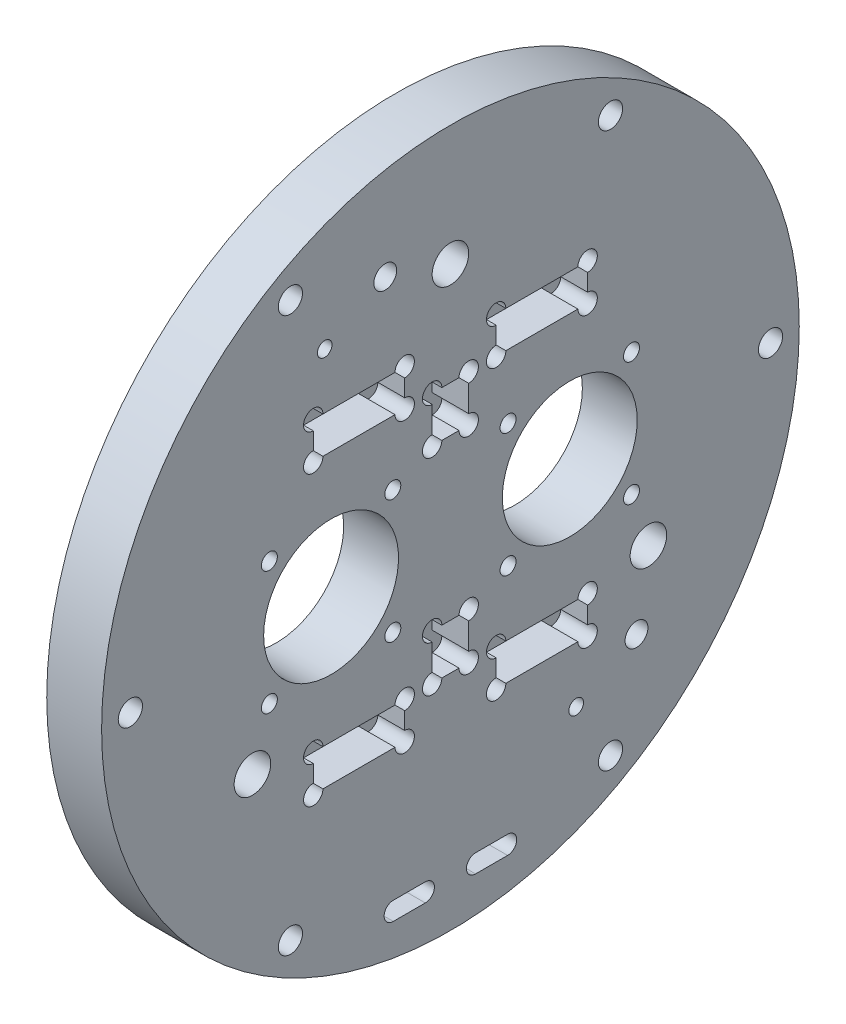
SolidWorks part; units mm, degrees
ref_plane "Front Plane" through (0, 0, 0) normal (0, 0, 1) x (1, 0, 0)
ref_plane "Top Plane" through (0, 0, 0) normal (0, 1, 0) x (1, 0, 0)
ref_plane "Right Plane" through (0, 0, 0) normal (1, 0, 0) x (0, 0, -1)
sketch "Sketch1" plane through (0, 0, 0) normal (1, 0, 0) x (0, 0, -1)
  line L0 (0, -76.29) -> (0, 76.29) construction
  line L1 (-76.29, 0) -> (76.29, 0) construction
  line L2 (26.1, 0) -> (39.5969, 13.4969) construction
  circle A0 centre (0, 0) radius 76.29
  circle A1 centre (0, 50) radius 4
  circle A2 centre (43.3013, -25) radius 4
  circle A3 centre (-43.3013, -25) radius 4
  circle A4 centre (26.1, 0) radius 14.75
  circle A5 centre (-26.1, 0) radius 14.75
  circle A6 centre (39.5969, 13.4969) radius 1.75
  circle A7 centre (39.5969, -13.4969) radius 1.75
  circle A8 centre (12.6031, -13.4969) radius 1.75
  circle A9 centre (12.6031, 13.4969) radius 1.75
  circle A10 centre (-39.5969, -13.4969) radius 1.75
  circle A11 centre (-12.6031, -13.4969) radius 1.75
  circle A12 centre (-12.6031, 13.4969) radius 1.75
  circle A13 centre (-39.5969, 13.4969) radius 1.75
  circle A14 centre (26.1, 0) radius 22.1 construction
  circle A15 centre (-26.1, 0) radius 22.1 construction
  circle A16 centre (-22.3739, -41.5) radius 2.5 construction
  point P12 (0, 0)
  point P29 (26.1, 0)
  point P37 (-4, 0)
  point P40 (4, 0)
  dimension "D1" = 152.58
  dimension "D2" = 8
  dimension "D5" = 29.5
  dimension "D7" = 3.5
  dimension "D11" = 44.2
  dimension "D3" = 50
  dimension "D4" = 3
  dimension "D6" = 8
  dimension "D8" = 19.0875
  dimension "D10" = 45
  dimension "D9" = 4
extrude "Boss-Extrude1" add sketch "Sketch1" along normal blind 12
sketch "Sketch2" plane through (12, 0, 0) normal (1, 0, 0) x (0, 0, -1)
  line L0 (-97.5918, 0) -> (102.3086, 0) construction
  line L1 (0, 96.3466) -> (0, -103.9448) construction
  line L2 (10, -27.5) -> (10, -35.5)
  line L3 (-30, -27.5) -> (-10, -27.5)
  line L4 (-30, -27.5) -> (-30, -35.5)
  line L5 (-30, -35.5) -> (-10, -35.5)
  line L6 (-10, -27.5) -> (-10, -35.5)
  line L7 (30, -27.5) -> (10, -27.5)
  line L8 (30, -27.5) -> (30, -35.5)
  line L9 (30, -35.5) -> (10, -35.5)
  line L10 (-30, 27.5) -> (-30, 35.5)
  line L11 (-30, 35.5) -> (-10, 35.5)
  line L12 (-10, 27.5) -> (-10, 35.5)
  line L13 (-30, 27.5) -> (-10, 27.5)
  line L14 (10, 27.5) -> (10, 35.5)
  line L15 (30, 35.5) -> (10, 35.5)
  line L16 (30, 27.5) -> (10, 27.5)
  line L17 (30, 27.5) -> (30, 35.5)
  line L18 (-4, -17.5) -> (4, -17.5)
  line L19 (-4, 27.5) -> (4, 27.5)
  line L20 (-4, 27.5) -> (-4, 17.5)
  line L21 (-4, 17.5) -> (4, 17.5)
  line L22 (4, 27.5) -> (4, 17.5)
  line L23 (-4, -27.5) -> (-4, -17.5)
  line L24 (-4, -27.5) -> (4, -27.5)
  line L25 (4, -27.5) -> (4, -17.5)
  line L26 (27.8787, -35.5) -> (30, -33.3787) construction
  line L27 (-42.3534, -68.29) -> (39.6493, -68.29) construction
  line L28 (-5.5, -68.29) -> (-5.5, -64.29)
  line L29 (12.5, -68.29) -> (5.5, -68.29)
  line L30 (12.5, -68.29) -> (12.5, -64.29)
  line L31 (12.5, -64.29) -> (5.5, -64.29)
  line L32 (5.5, -68.29) -> (5.5, -64.29)
  line L33 (-12.5, -64.29) -> (-5.5, -64.29)
  line L34 (-12.5, -68.29) -> (-12.5, -64.29)
  line L35 (-12.5, -68.29) -> (-5.5, -68.29)
  circle A0 centre (30, -35.5) radius 2.1213 construction
  circle A1 centre (0, 0) radius 76.29 construction
  point P23 (0, 27.5)
  point P31 (30, -33.3787)
  point P32 (0, -76.29)
  point P33 (27.8787, -35.5)
  dimension "D1" = 27.5
  dimension "D2" = 8
  dimension "D3" = 20
  dimension "D4" = 20
  dimension "D5" = 8
  dimension "D6" = 10
  dimension "D7" = 8
  dimension "D8" = 4
  dimension "D9" = 7
  dimension "D10" = 25
extrude "Cut-Extrude1" cut sketch "Sketch2" against normal blind 8
sketch "Sketch3" plane through (0, 0, 0) normal (-1, 0, 0) x (0, 0, 1)
  circle A0 centre (-70, 0) radius 2.65
  circle A1 centre (-35, 60.6218) radius 2.65
  circle A2 centre (35, 60.6218) radius 2.65
  circle A3 centre (70, 0) radius 2.65
  circle A4 centre (35, -60.6218) radius 2.65
  circle A5 centre (-35, -60.6218) radius 2.65
  point P16 (0, 0)
  dimension "D2" = 5.3
  dimension "D1" = 70
  dimension "D3" = 6
extrude "Cut-Extrude2" cut sketch "Sketch3" against normal up to next
sketch "Sketch4" plane through (12, 0, 0) normal (1, 0, 0) x (0, 0, -1)
  line L0 (12.5, -68.29) -> (12.5, -64.29) construction
  line L2 (5.5, -64.29) -> (5.5, -68.29) construction
  line L3 (-5.5, -68.29) -> (-5.5, -64.29) construction
  line L4 (-12.5, -64.29) -> (-12.5, -68.29) construction
  circle A0 centre (-10, -35.5) radius 2.1213
  circle A1 centre (-10, -27.5) radius 2.1213
  circle A2 centre (-30, -27.5) radius 2.1213
  circle A3 centre (-30, -35.5) radius 2.1213
  circle A4 centre (12.5, -66.29) radius 2
  circle A5 centre (5.5, -66.29) radius 2
  circle A6 centre (-5.5, -66.29) radius 2
  circle A7 centre (-12.5, -66.29) radius 2
  circle A12 centre (10, -35.5) radius 2.1213
  circle A13 centre (10, -27.5) radius 2.1213
  circle A14 centre (30, -27.5) radius 2.1213
  circle A15 centre (30, -35.5) radius 2.1213
  circle A16 centre (4, -27.5) radius 2.1213
  circle A17 centre (-4, -27.5) radius 2.1213
  circle A18 centre (-4, -17.5) radius 2.1213
  circle A19 centre (4, -17.5) radius 2.1213
  circle A20 centre (4, 27.5) radius 2.1213
  circle A21 centre (-4, 27.5) radius 2.1213
  circle A22 centre (-4, 17.5) radius 2.1213
  circle A23 centre (4, 17.5) radius 2.1213
  circle A24 centre (10, 27.5) radius 2.1213
  circle A25 centre (10, 35.5) radius 2.1213
  circle A26 centre (30, 35.5) radius 2.1213
  circle A27 centre (30, 27.5) radius 2.1213
  circle A28 centre (-10, 35.5) radius 2.1213
  circle A29 centre (-10, 27.5) radius 2.1213
  circle A30 centre (-30, 27.5) radius 2.1213
  circle A31 centre (-30, 35.5) radius 2.1213
  point P2 (-12.1213, -35.5)
  point P5 (-10, -33.3787)
  dimension "D1" = 3
extrude "Cut-Extrude3" cut sketch "Sketch4" against normal up to surface (8 mm away) up to face at (4, -31.5, 20)
sketch "Sketch5" plane through (0, 0, 0) normal (-1, 0, 0) x (0, 0, 1)
  line L0 (-35, -60.6218) -> (35, 60.6218) construction
  line L1 (0, 113.7201) -> (0, -122.5246) construction
  line L2 (-128.5049, 0) -> (121.7105, 0) construction
  circle A1 centre (-27.5, -47.6314) radius 1.6
  circle A2 centre (27.5, 47.6314) radius 1.6
  point P7 (0, 0)
  point P8 (-35, -60.6218)
  point P9 (0, 0)
  point P12 (0, 0)
  point P13 (0, 0)
  dimension "D2" = 3.2
  dimension "D1" = 2
  dimension "D3" = 15
extrude "Cut-Extrude4" cut sketch "Sketch5" against normal up to next
sketch "Sketch9" plane through (12, 0, 0) normal (1, 0, 0) x (0, 0, -1)
  line L1 (12.1213, -35.5) -> (27.8787, -35.5) construction
  circle A0 centre (27.5, -47.6314) radius 1.6 construction
  circle A2 centre (-14.2543, 54.6707) radius 2.5
  circle A4 centre (40.6963, -40.5) radius 2.5
  circle A7 centre (-27.5, 47.6314) radius 1.6 construction
  circle A8 centre (0, 50) radius 4 construction
  point P0 (-13.6876, 53.4809)
  dimension "D1" = 5
  dimension "D2" = 5
  dimension "D4" = 15
  dimension "D3" = 5
  dimension "D5" = 15
  dimension "D6" = 15
extrude "Cut-Extrude6" cut sketch "Sketch9" against normal up to next
